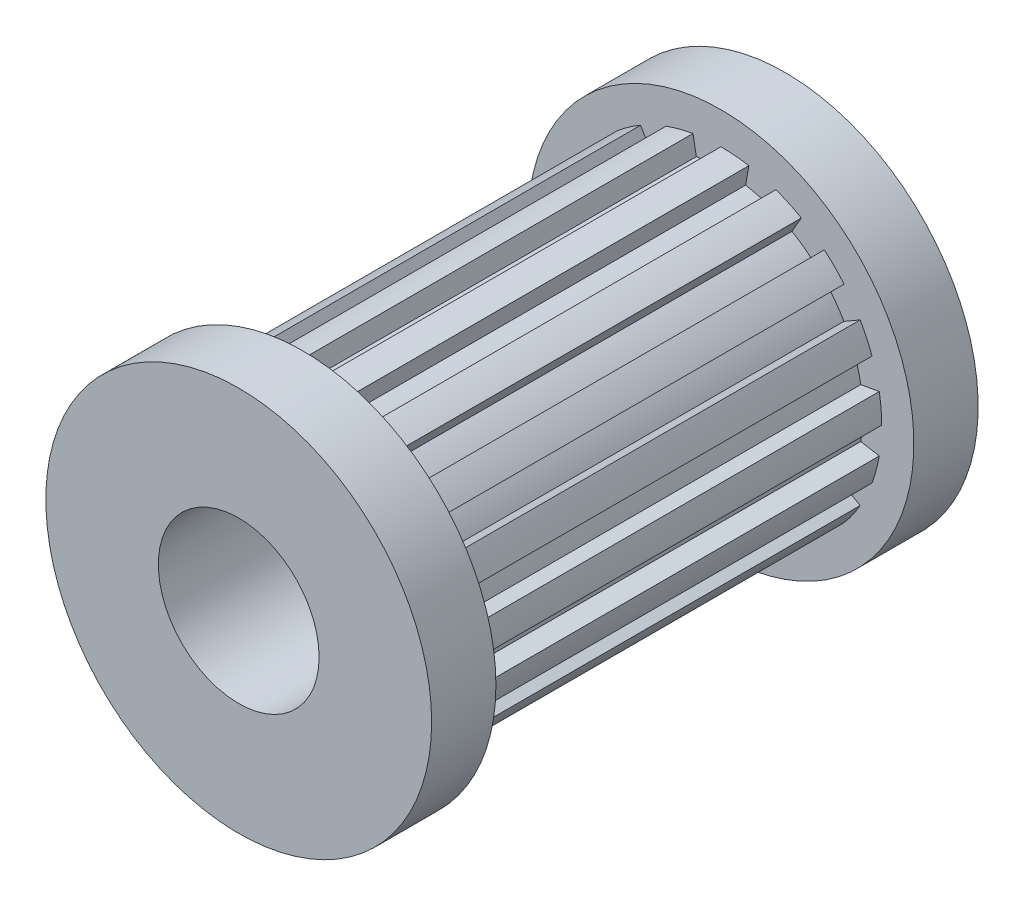
SolidWorks part; units mm, degrees
ref_plane "Alzado" through (0, 0, 0) normal (0, 0, 1) x (1, 0, 0)
ref_plane "Planta" through (0, 0, 0) normal (0, 1, 0) x (1, 0, 0)
ref_plane "Vista lateral" through (0, 0, 0) normal (1, 0, 0) x (0, 0, -1)
sketch "Croquis1" plane through (0, 0, 0) normal (0, 0, 1) x (1, 0, 0)
  line L0 (0, 4.4163) -> (0, 5)
  line L2 (1.5105, 4.15) -> (1.7101, 4.6985)
  line L4 (2.8388, 3.3831) -> (3.2139, 3.8302)
  line L6 (3.8246, 2.2082) -> (4.3301, 2.5)
  line L8 (4.3492, 0.7669) -> (4.924, 0.8682)
  line L10 (4.3492, -0.7669) -> (4.924, -0.8682)
  line L12 (3.8246, -2.2082) -> (4.3301, -2.5)
  line L14 (2.8388, -3.3831) -> (3.2139, -3.8302)
  line L16 (1.5105, -4.15) -> (1.7101, -4.6985)
  line L18 (0, -4.4163) -> (0, -5)
  line L20 (-1.5105, -4.15) -> (-1.7101, -4.6985)
  line L22 (-2.8388, -3.3831) -> (-3.2139, -3.8302)
  line L24 (-3.8246, -2.2082) -> (-4.3301, -2.5)
  line L26 (-4.3492, -0.7669) -> (-4.924, -0.8682)
  line L28 (-4.3492, 0.7669) -> (-4.924, 0.8682)
  line L30 (-3.8246, 2.2082) -> (-4.3301, 2.5)
  line L32 (-2.8388, 3.3831) -> (-3.2139, 3.8302)
  line L34 (-1.5105, 4.15) -> (-1.7101, 4.6985)
  line L36 (-2.2082, -3.8246) -> (-2.5, -4.3301)
  line L37 (-3.3831, -2.8388) -> (-3.8302, -3.2139)
  line L38 (-4.15, -1.5105) -> (-4.6985, -1.7101)
  line L39 (-4.4163, 0) -> (-5, 0)
  line L40 (-4.15, 1.5105) -> (-4.6985, 1.7101)
  line L41 (-3.3831, 2.8388) -> (-3.8302, 3.2139)
  line L42 (-2.2082, 3.8246) -> (-2.5, 4.3301)
  line L43 (-0.7669, 4.3492) -> (-0.8682, 4.924)
  line L44 (0.7669, 4.3492) -> (0.8682, 4.924)
  line L45 (2.2082, 3.8246) -> (2.5, 4.3301)
  line L46 (3.3831, 2.8388) -> (3.8302, 3.2139)
  line L47 (4.15, 1.5105) -> (4.6985, 1.7101)
  line L48 (4.4163, 0) -> (5, 0)
  line L49 (4.15, -1.5105) -> (4.6985, -1.7101)
  line L50 (3.3831, -2.8388) -> (3.8302, -3.2139)
  line L51 (2.2082, -3.8246) -> (2.5, -4.3301)
  line L52 (0.7669, -4.3492) -> (0.8682, -4.924)
  line L53 (-0.7669, -4.3492) -> (-0.8682, -4.924)
  arc A0 (0.8682, 4.924) -> (0, 5) centre (0, 0) ccw
  circle A1 centre (0, 0) radius 6 construction
  circle A2 centre (0, 0) radius 2.5
  arc A4 (2.5, 4.3301) -> (1.7101, 4.6985) centre (0, 0) ccw
  arc A5 (3.8302, 3.2139) -> (3.2139, 3.8302) centre (0, 0) ccw
  arc A6 (4.6985, 1.7101) -> (4.3301, 2.5) centre (0, 0) ccw
  arc A7 (5, 0) -> (4.924, 0.8682) centre (0, 0) ccw
  arc A8 (4.6985, -1.7101) -> (4.924, -0.8682) centre (0, 0) ccw
  arc A9 (3.8302, -3.2139) -> (4.3301, -2.5) centre (0, 0) ccw
  arc A10 (2.5, -4.3301) -> (3.2139, -3.8302) centre (0, 0) ccw
  arc A11 (0.8682, -4.924) -> (1.7101, -4.6985) centre (0, 0) ccw
  arc A12 (-0.8682, -4.924) -> (0, -5) centre (0, 0) ccw
  arc A13 (-2.5, -4.3301) -> (-1.7101, -4.6985) centre (0, 0) ccw
  arc A14 (-3.8302, -3.2139) -> (-3.2139, -3.8302) centre (0, 0) ccw
  arc A15 (-4.6985, -1.7101) -> (-4.3301, -2.5) centre (0, 0) ccw
  arc A16 (-5, 0) -> (-4.924, -0.8682) centre (0, 0) ccw
  arc A17 (-4.6985, 1.7101) -> (-4.924, 0.8682) centre (0, 0) ccw
  arc A18 (-3.8302, 3.2139) -> (-4.3301, 2.5) centre (0, 0) ccw
  arc A19 (-2.5, 4.3301) -> (-3.2139, 3.8302) centre (0, 0) ccw
  arc A20 (-0.8682, 4.924) -> (-1.7101, 4.6985) centre (0, 0) ccw
  arc A21 (-3.8246, -2.2082) -> (-3.3831, -2.8388) centre (0, 0) ccw
  arc A22 (-4.3492, -0.7669) -> (-4.15, -1.5105) centre (0, 0) ccw
  arc A23 (-4.3492, 0.7669) -> (-4.4163, 0) centre (0, 0) ccw
  arc A24 (-3.8246, 2.2082) -> (-4.15, 1.5105) centre (0, 0) ccw
  arc A25 (-2.8388, 3.3831) -> (-3.3831, 2.8388) centre (0, 0) ccw
  arc A26 (0, 4.4163) -> (-0.7669, 4.3492) centre (0, 0) ccw
  arc A27 (-1.5105, 4.15) -> (-2.2082, 3.8246) centre (0, 0) ccw
  arc A28 (1.5105, 4.15) -> (0.7669, 4.3492) centre (0, 0) ccw
  arc A29 (2.8388, 3.3831) -> (2.2082, 3.8246) centre (0, 0) ccw
  arc A30 (3.8246, 2.2082) -> (3.3831, 2.8388) centre (0, 0) ccw
  arc A31 (4.3492, 0.7669) -> (4.15, 1.5105) centre (0, 0) ccw
  arc A32 (3.8246, -2.2082) -> (4.15, -1.5105) centre (0, 0) ccw
  arc A33 (2.8388, -3.3831) -> (3.3831, -2.8388) centre (0, 0) ccw
  arc A34 (1.5105, -4.15) -> (2.2082, -3.8246) centre (0, 0) ccw
  arc A35 (0, -4.4163) -> (0.7669, -4.3492) centre (0, 0) ccw
  arc A36 (-1.5105, -4.15) -> (-0.7669, -4.3492) centre (0, 0) ccw
  arc A37 (-2.8388, -3.3831) -> (-2.2082, -3.8246) centre (0, 0) ccw
  arc A38 (4.3492, -0.7669) -> (4.4163, 0) centre (0, 0) ccw
  point P60 (0, 0)
  dimension "D1" = 5
  dimension "D2" = 10
  dimension "D3" = 12
  dimension "D5" = 18
extrude "Saliente-Extruir1" add sketch "Croquis1" along normal blind 7.5 and the other way blind 7.5
sketch "Croquis2" plane through (0, 0, 7.5) normal (0, 0, 1) x (1, 0, 0)
  circle A0 centre (0, 0) radius 6
  circle A1 centre (0, 0) radius 2.5
  dimension "D1" = 12
extrude "Saliente-Extruir2" add sketch "Croquis2" against normal blind 2
sketch "Croquis3" plane through (0, 0, -7.5) normal (0, 0, -1) x (-1, 0, 0)
  circle A0 centre (0, 0) radius 6
  circle A1 centre (0, 0) radius 2.5
extrude "Saliente-Extruir3" add sketch "Croquis3" along normal blind 2
